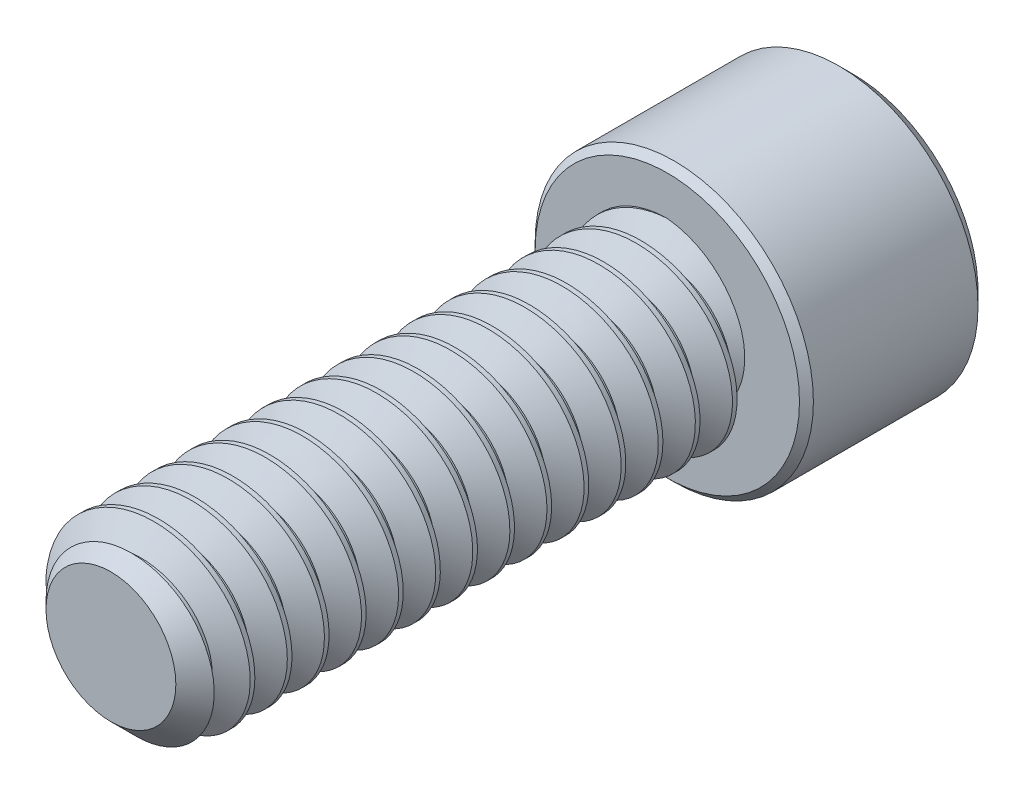
SolidWorks part; units mm, degrees
ref_plane "Front Plane" through (0, 0, 0) normal (0, 0, 1) x (1, 0, 0)
ref_plane "Top Plane" through (0, 0, 0) normal (0, 1, 0) x (1, 0, 0)
ref_plane "Right Plane" through (0, 0, 0) normal (1, 0, 0) x (0, 0, -1)
sketch "Sketch0" plane through (0, 0, 0) normal (1, 0, 0) x (0, 0, -1)
  line L0 (0, 0) -> (19.05, 0) construction
  point P2 (25.4, 0)
  point P4 (0, 0)
  dimension "D1" = 19.05
  dimension "D2" = 6.35
  dimension "Min Thread" = 0
sketch "Sketch1" plane through (0, 0, 0) normal (0, 0, 1) x (1, 0, 0)
  circle A0 centre (0, 0) radius 3.175
  dimension "OD" = 6.35
extrude "Extrude1" add sketch "Sketch1" against normal blind 19.05
sketch "Sketch2" plane through (0, 0, 0) normal (0, 0, 1) x (1, 0, 0)
  circle A0 centre (0, 0) radius 3.175 construction
  circle A1 centre (0, 0) radius 3.175
curve "Helix/Spiral1" pitch 1.27 height 20.32 turns 16 parameters "pitch"=1.27
chamfer "Chamfer3" distance 0.9525 angle 45 1 edges at (3.175, 0, 0)
sketch "Sketch3" plane through (0, 0, 0) normal (1, 0, 0) x (0, 0, -1)
  line L0 (-1.1113, 3.175) -> (-0.635, 2.3501)
  line L1 (-0.635, 2.3501) -> (-0.4763, 2.3501)
  line L2 (-0.4763, 2.3501) -> (0, 3.175)
  line L3 (-1.1113, 3.175) -> (0, 3.175)
  line L4 (-0.5556, 3.175) -> (-0.5556, 2.3501) construction
  line L5 (-0.8731, 2.7626) -> (-0.2381, 2.7626) construction
  line L6 (0, 3.175) -> (0, -3.175) construction
  dimension "D1" = 0.1588
  dimension "D2" = 0.635
  dimension "D3" = 60
sweep "Cut-Sweep1" cut profiles "Sketch3" path "Helix/Spiral1"
sketch "Sketch5" plane through (0, 0, 0) normal (1, 0, 0) x (0, 0, -1)
  line L0 (19.05, -2.3728) -> (19.05, 2.2654) construction
  line L1 (19.05, 3.175) -> (0, 3.175)
  line L2 (19.05, 3.175) -> (19.05, 0)
  line L3 (19.05, 0) -> (-1.1556, 0)
  line L4 (0, 0) -> (19.05, 0) construction
  line L5 (0, 3.175) -> (-1.1556, 0)
  line L6 (0, 0) -> (21.59, 0) construction
  dimension "D1" = 70
  dimension "D3" = 2.54
revolve "partially thread" [suppressed] add sketch "Sketch5" angle 360 about L6
sketch "Sketch6" plane through (0, 0, -19.05) normal (0, 0, -1) x (-1, 0, 0)
  circle A0 centre (0, 0) radius 4.7625
  dimension "head dia" = 9.525
extrude "Extrude2" add sketch "Sketch6" along normal blind 6.35
sketch "Sketch7" plane through (0, 0, -25.4) normal (0, 0, -1) x (-1, 0, 0)
  line L1 (0, 2.7496) -> (-2.3813, 1.3748)
  line L2 (-2.3813, 1.3748) -> (-2.3813, -1.3748)
  line L3 (-2.3813, -1.3748) -> (0, -2.7496)
  line L4 (0, -2.7496) -> (2.3813, -1.3748)
  line L5 (2.3813, -1.3748) -> (2.3813, 1.3748)
  line L6 (2.3813, 1.3748) -> (0, 2.7496)
  circle A0 centre (0, 0) radius 2.3813 construction
  dimension "hex dia" = 4.7625
extrude "Cut-Extrude1" cut sketch "Sketch7" against normal blind 3.5719
sketch "Sketch8" plane through (0, 0, -25.4) normal (0, 0, -1) x (-1, 0, 0)
  circle A0 centre (0, 0) radius 2.7496
extrude "Cut-Extrude2" cut sketch "Sketch8" against normal through all draft 45
chamfer "Chamfer1" distance 0.4763 angle 45 1 edges at (-4.7625, 0, -25.4)
chamfer "Chamfer2" distance 0.2381 angle 45 1 edges at (-4.7625, 0, -19.05)
sketch "Sketch9" plane through (0, 0, 0) normal (1, 0, 0) x (0, 0, -1)
  line L0 (0, 3.175) -> (0, -3.175) construction
  line L1 (3.175, 3.175) -> (3.175, -3.175) construction
  line L2 (25.4, 4.7625) -> (25.4, -4.7625) construction
  line L3 (19.05, 4.7625) -> (19.05, -4.7625) construction
  line L4 (19.05, 4.5244) -> (19.05, -4.5244) construction
  line L5 (25.4, -4.2862) -> (25.4, 4.2862) construction
  line L6 (19.05, -4.7625) -> (19.05, 4.7625) construction
  line L7 (0, 2.2225) -> (0, -2.2225) construction
  line L8 (-1.1113, 3.175) -> (0, 3.175) construction
  line L9 (3.175, 0) -> (0, 0) construction
  dimension "D1" = 3.175
equation "\"D3@Helix/Spiral1\" = \"screw length@Extrude1\"+\"pitch@Helix/Spiral1\""
equation "\"D1@Sketch3\" = \"pitch@Helix/Spiral1\"*.125"
equation "\"D2@Sketch3\" = \"pitch@Helix/Spiral1\"*.5"
equation "\"D1@Cut-Extrude1\" = \"hex dia@Sketch7\"*.75"
equation "\"D1@Chamfer1\" = \"head dia@Sketch6\"*.05"
equation "\"D1@Sketch9\" = \"pitch@Helix/Spiral1\"*2.50"
equation "\"D1@Chamfer2\" = \"D1@Chamfer1\"/2"
equation "\"D1@Chamfer3\" = \"pitch@Helix/Spiral1\"*.750"
equation "\"D1@Sketch0\" = \"screw length@Extrude1\""
equation "\"D2@Sketch0\" = \"head depth@Extrude2\""
